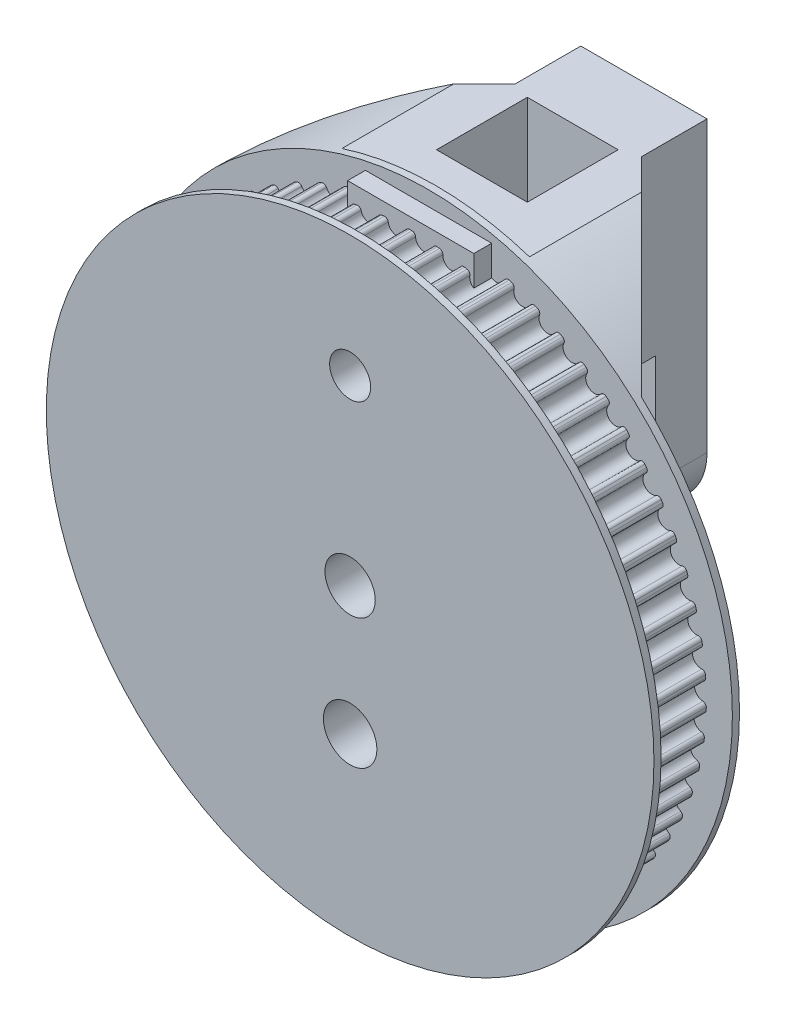
SolidWorks part; units mm, degrees
other "Markup1"
sketch "Sketch12" plane through (-30, -58, 49.7) normal (-0.8709, -0.4905, 0.0319) x (-0.1533, 0.2093, -0.9658)
other "Markup2"
sketch "Sketch14" plane through (30, -60, 49.7) normal (0.6168, -0.7172, 0.3243) x (-0.4689, -0.0038, 0.8832)
material "PETG"
ref_plane "Front Plane" through (0, 0, 0) normal (0, 0, 1) x (1, 0, 0)
ref_plane "Top Plane" through (0, 0, 0) normal (0, 1, 0) x (1, 0, 0)
ref_plane "Right Plane" through (0, 0, 0) normal (1, 0, 0) x (0, 0, -1)
sketch "Sketch1" plane through (0, 0, 0) normal (0, 1, 0) x (1, 0, 0)
  line L1 (-12.7375, -12.7375) -> (12.7375, -12.7375)
  line L2 (-12.7375, -12.7375) -> (-12.7375, 12.7375)
  line L3 (-12.7375, 12.7375) -> (12.7375, 12.7375)
  line L4 (12.7375, -12.7375) -> (12.7375, 12.7375)
  line L5 (-17.7, -17.7) -> (17.7, -17.7)
  line L6 (-17.7, -17.7) -> (-17.7, 17.7)
  line L7 (-17.7, 17.7) -> (17.7, 17.7)
  line L8 (17.7, -17.7) -> (17.7, 17.7)
  point P8 (0, -17.7)
  point P9 (0, -12.7375)
  point P12 (-17.7, 0)
  point P13 (-12.7375, 0)
  dimension "D1" = 25.475
  dimension "D2" = 35.4
extrude "Boss-Extrude1" add sketch "Sketch1" along normal blind 47.0375
extrude "Boss-Extrude2" add sketch "Sketch1<3>" against normal blind 14.9625 contours L1 L4 L3 L2 | L5 L8 L7 L6 L4 L1 L2 L3 region at (0, 0, 0) region at (-17.1994, 0, 0)
sketch "Sketch1<3>" plane through (0, 0, 0) normal (0, 1, 0) x (1, 0, 0) same geometry as "Sketch1"
sketch "Sketch3" plane through (0, 0, 0) normal (0, -1, 0) x (-1, 0, 0)
  circle A0 centre (0, 0) radius 3.15
  dimension "D1" = 6.3
extrude "Cut-Extrude1" cut sketch "Sketch3" along normal through all
sketch "Sketch13" plane through (0, -14.9625, 0) normal (0, -1, 0) x (1, 0, 0)
  circle A0 centre (0, 0) radius 5.5
  dimension "D1" = 11
extrude "Cut-Extrude4" cut sketch "Sketch13" against normal offset from surface (6.9625 mm away) 8 up to face at (0, 0, -3.15)
sketch "Sketch4" plane through (0, 0, 17.7) normal (0, 0, 1) x (1, 0, 0)
  line L0 (17.7, 47.0375) -> (17.7, -14.9625) construction
  line L1 (-17.7, 47.0375) -> (-17.7, -14.9625) construction
  line L2 (17.7, -34.0125) -> (17.7, -14.9625)
  line L3 (-17.7, -34.0125) -> (-17.7, -14.9625)
  line L5 (17.7, 47.0375) -> (-17.7, 47.0375)
  line L6 (17.7, 47.0375) -> (17.7, -14.9625)
  line L8 (-17.7, 47.0375) -> (-17.7, -14.9625)
  line L9 (-17.7, -14.9625) -> (17.7, -14.9625) construction
  line L10 (-17.7, 47.0375) -> (17.7, 47.0375) construction
  arc A0 (-17.7, -34.0125) -> (17.7, -34.0125) centre (0, -34.0125) ccw
  circle A1 centre (0, -34.0125) radius 7.05
  dimension "D2" = 14.1
  dimension "D1" = 19.05
extrude "Boss-Extrude3" add sketch "Sketch4" along normal blind 15
sketch "Sketch6" plane through (0, 0, 17.7) normal (0, 0, -1) x (-1, 0, 0)
  line L0 (17.7, -34.0125) -> (17.7, -14.9625)
  line L1 (17.7, -14.9625) -> (-17.7, -14.9625)
  line L2 (-17.7, -14.9625) -> (-17.7, -34.0125)
  arc A0 (-17.7, -34.0125) -> (17.7, -34.0125) centre (0, -34.0125) ccw
  arc A4 (-17.7, -34.0125) -> (17.7, -34.0125) centre (0, -34.0125) ccw construction
extrude "Cut-Extrude2" cut sketch "Sketch6" against normal blind 0.5375
sketch "Sketch7" plane through (0, 0, 18.2375) normal (0, 0, -1) x (-1, 0, 0)
  circle A0 centre (0, -34.0125) radius 11.0375
  arc A1 (-17.7, -34.0125) -> (17.7, -34.0125) centre (0, -34.0125) ccw construction
  dimension "D1" = 22.075
extrude "Cut-Extrude3" cut sketch "Sketch7" against normal blind 7
mirror "Mirror1" about plane through (0, 0, 0) normal (0, 0, 1) of "Boss-Extrude3", "Cut-Extrude2", "Cut-Extrude1", "Cut-Extrude3"
sketch "Sketch18" plane through (0, 0, 0) normal (0, 0, 1) x (1, 0, 0)
  line L0 (0, -13.5166) -> (-17.7, -3.2975)
  line L1 (-17.7, -3.2975) -> (-35.45, -34.0414) construction
  line L2 (-35.45, -34.0414) -> (-8.875, -49.3845) construction
  line L3 (-17.7, 47.0375) -> (-17.7, -34.0125) construction
  line L4 (0, -35.0322) -> (0, -50035.0322) construction
  line L5 (-17.7, -3.2975) -> (-17.7, -14.9625)
  line L6 (17.7, -34.0125) -> (17.7, 47.0375) construction
  line L7 (17.7, -3.2975) -> (0, -13.5166)
  line L10 (17.7, -14.9625) -> (17.7, -3.2975)
  line L11 (-17.7, -14.9625) -> (17.7, -14.9625)
  line L12 (-5.5, -14.9625) -> (5.5, -14.9625) construction
  circle A0 centre (0, -34.0125) radius 17.75 construction
  arc A2 (-17.7, -34.0125) -> (17.7, -34.0125) centre (0, -34.0125) ccw construction
  dimension "D2" = 120
  dimension "D1" = 35.5
extrude "Cut-Extrude10" cut sketch "Sketch18" along normal up to surface and the other way up to surface up to face at (-11.0375, -34.0125, 18.2375) other way up to face at (-11.0375, -34.0125, -18.2375)
ref_plane "Plane1" through (0, 0, 27.7) normal (0, 0, 1) x (1, 0, 0)
sketch "Sketch9" plane through (0, 0, 27.7) normal (0, 0, 1) x (1, 0, 0)
  circle A0 centre (0, -34.0125) radius 85.2141
  circle A1 centre (0, -34.0125) radius 7.05 construction
  circle A2 centre (0, -34.0125) radius 7.05
  dimension "D1" = 170.4282
extrude "Boss-Extrude4" add sketch "Sketch9" against normal blind 2 contours A0 region at (-82.8039, -34.0125, 27.7)
sketch "Sketch10" plane through (0, 0, 27.7) normal (0, 0, -1) x (-1, 0, 0)
  line L0 (0, -41.0625) -> (0, -50041.0625) construction
  line L1 (0, -34.0125) -> (-3.9983, -114.1269) construction
  line L2 (0, -34.0125) -> (3.9983, -114.1269) construction
  circle A0 centre (0, -34.0125) radius 80.2141 construction
  circle A1 centre (0, -34.0125) radius 7.05
  circle A2 centre (0, -34.0125) radius 85.2141 construction
  circle A3 centre (0, -34.0125) radius 7.05 construction
  arc A4 (2.4815, -110.9206) -> (-2.4815, -110.9206) centre (0, -111.1266) ccw
  arc A5 (-3.5233, -111.8369) -> (-2.4815, -110.9206) centre (-3.478, -110.8379) ccw
  circle A6 centre (0, -34.0125) radius 77.9041 construction
  arc A7 (2.4815, -110.9206) -> (3.5233, -111.8369) centre (3.478, -110.8379) ccw
  arc A8 (3.5233, -111.8369) -> (3.8832, -111.8198) centre (0, -34.0125) ccw
  arc A9 (-3.8832, -111.8198) -> (-3.5233, -111.8369) centre (0, -34.0125) ccw
  arc A10 (-11.611, -111.0465) -> (-11.2546, -111.0993) centre (0, -34.0125) ccw
  arc A11 (-11.2546, -111.0993) -> (-10.1267, -110.2914) centre (-11.1101, -110.1098) ccw
  arc A12 (-5.1884, -110.7855) -> (-10.1267, -110.2914) centre (-7.6781, -110.7434) ccw
  arc A13 (-5.1884, -110.7855) -> (-4.243, -111.801) centre (-4.1886, -110.8024) ccw
  arc A14 (-4.243, -111.801) -> (-3.8832, -111.8198) centre (0, -34.0125) ccw
  arc A15 (-19.2234, -109.5076) -> (-18.874, -109.5957) centre (0, -34.0125) ccw
  arc A16 (-18.874, -109.5957) -> (-17.6713, -108.904) centre (-18.6317, -108.6255) ccw
  arc A17 (-12.8068, -109.8874) -> (-17.6713, -108.904) centre (-15.2799, -109.5976) ccw
  arc A18 (-12.8068, -109.8874) -> (-11.9672, -110.9919) centre (-11.8136, -110.0038) ccw
  arc A19 (-11.9672, -110.9919) -> (-11.611, -111.0465) centre (0, -34.0125) ccw
  arc A20 (-26.6448, -107.2184) -> (-26.3059, -107.3409) centre (0, -34.0125) ccw
  arc A21 (-26.3059, -107.3409) -> (-25.0403, -106.7724) centre (-25.9682, -106.3996) ccw
  arc A22 (-20.2978, -108.2352) -> (-25.0403, -106.7724) centre (-22.7298, -107.7006) ccw
  arc A23 (-20.2978, -108.2352) -> (-19.5724, -109.4179) centre (-19.3212, -108.4499) ccw
  arc A24 (-19.5724, -109.4179) -> (-19.2234, -109.5076) centre (0, -34.0125) ccw
  arc A25 (-33.8013, -104.2017) -> (-33.4763, -104.3573) centre (0, -34.0125) ccw
  arc A26 (-33.4763, -104.3573) -> (-32.1604, -103.9176) centre (-33.0466, -103.4543) ccw
  arc A27 (-27.5872, -105.8454) -> (-32.1604, -103.9176) centre (-29.9538, -105.0713) ccw
  arc A28 (-27.5872, -105.8454) -> (-26.9831, -107.0944) centre (-26.6367, -106.1563) ccw
  arc A29 (-26.9831, -107.0944) -> (-26.6448, -107.2184) centre (0, -34.0125) ccw
  arc A30 (-40.6219, -100.4874) -> (-40.314, -100.6745) centre (0, -34.0125) ccw
  arc A31 (-40.314, -100.6745) -> (-38.9609, -100.3681) centre (-39.7965, -99.8188) ccw
  arc A32 (-34.6023, -102.7416) -> (-38.9609, -100.3681) centre (-36.8801, -101.7358) ccw
  arc A33 (-34.6023, -102.7416) -> (-34.1256, -104.0446) centre (-33.6876, -103.1456) ccw
  arc A34 (-34.1256, -104.0446) -> (-33.8013, -104.2017) centre (0, -34.0125) ccw
  arc A35 (-47.0388, -96.1124) -> (-46.7511, -96.3293) centre (0, -34.0125) ccw
  arc A36 (-46.7511, -96.3293) -> (-45.3742, -96.1591) centre (-46.151, -95.5294) ccw
  arc A37 (-41.2736, -98.9548) -> (-45.3742, -96.1591) centre (-43.4399, -97.7272) ccw
  arc A38 (-41.2736, -98.9548) -> (-40.929, -100.2987) centre (-40.4036, -99.4479) ccw
  arc A39 (-40.929, -100.2987) -> (-40.6219, -100.4874) centre (0, -34.0125) ccw
  arc A40 (-52.9882, -91.1202) -> (-52.7235, -91.3647) centre (0, -34.0125) ccw
  arc A41 (-52.7235, -91.3647) -> (-51.3365, -91.3325) centre (-52.0467, -90.6285) ccw
  arc A42 (-47.5347, -94.5226) -> (-51.3365, -91.3325) centre (-49.568, -93.0853) ccw
  arc A43 (-47.5347, -94.5226) -> (-47.3256, -95.8941) centre (-46.7181, -95.0998) ccw
  arc A44 (-47.3256, -95.8941) -> (-47.0388, -96.1124) centre (0, -34.0125) ccw
  arc A45 (-58.411, -85.5605) -> (-58.172, -85.8302) centre (0, -34.0125) ccw
  arc A46 (-58.172, -85.8302) -> (-56.7886, -85.9362) centre (-57.4253, -85.165) ccw
  arc A47 (-53.3233, -89.489) -> (-56.7886, -85.9362) centre (-55.2034, -87.8564) ccw
  arc A48 (-53.3233, -89.489) -> (-53.2518, -90.8745) centre (-52.5683, -90.1446) ccw
  arc A49 (-53.2518, -90.8745) -> (-52.9882, -91.1202) centre (0, -34.0125) ccw
  arc A50 (-63.2533, -79.4885) -> (-63.0423, -79.7806) centre (0, -34.0125) ccw
  arc A51 (-63.0423, -79.7806) -> (-61.6764, -80.0238) centre (-62.233, -79.1931) ccw
  arc A52 (-58.582, -83.904) -> (-61.6764, -80.0238) centre (-60.2902, -82.0923) ccw
  arc A53 (-58.582, -83.904) -> (-58.6488, -85.2898) centre (-57.896, -84.6316) ccw
  arc A54 (-58.6488, -85.2898) -> (-58.411, -85.5605) centre (0, -34.0125) ccw
  arc A55 (-67.4669, -72.9645) -> (-67.286, -73.2762) centre (0, -34.0125) ccw
  arc A56 (-67.286, -73.2762) -> (-65.9511, -73.6542) centre (-66.4223, -72.7722) ccw
  arc A57 (-63.2585, -77.8232) -> (-65.9511, -73.6542) centre (-64.7778, -75.8505) ccw
  arc A58 (-63.2585, -77.8232) -> (-63.463, -79.1955) centre (-62.6483, -78.6155) ccw
  arc A59 (-63.463, -79.1955) -> (-63.2533, -79.4885) centre (0, -34.0125) ccw
  arc A60 (-71.01, -66.0534) -> (-70.8611, -66.3816) centre (0, -34.0125) ccw
  arc A61 (-70.8611, -66.3816) -> (-69.5704, -66.8906) centre (-69.9515, -65.9661) ccw
  arc A62 (-67.3063, -71.307) -> (-69.5704, -66.8906) centre (-68.6217, -69.1928) ccw
  arc A63 (-67.3063, -71.307) -> (-67.6464, -72.6521) centre (-66.778, -72.1561) ccw
  arc A64 (-67.6464, -72.6521) -> (-67.4669, -72.9645) centre (0, -34.0125) ccw
  arc A65 (-73.8474, -58.8239) -> (-73.7319, -59.1652) centre (0, -34.0125) ccw
  arc A66 (-73.7319, -59.1652) -> (-72.4983, -59.8003) centre (-72.7854, -58.8424) ccw
  arc A67 (-70.6852, -64.4201) -> (-72.4983, -59.8003) centre (-71.7835, -62.1854) ccw
  arc A68 (-70.6852, -64.4201) -> (-71.1575, -65.7247) centre (-70.2441, -65.3176) ccw
  arc A69 (-71.1575, -65.7247) -> (-71.01, -66.0534) centre (0, -34.0125) ccw
  arc A70 (-75.9509, -51.3478) -> (-75.8699, -51.6989) centre (0, -34.0125) ccw
  arc A71 (-75.8699, -51.6989) -> (-74.7057, -52.4536) centre (-74.896, -51.4719) ccw
  arc A72 (-73.3615, -57.2311) -> (-74.7057, -52.4536) centre (-74.2319, -54.8981) ccw
  arc A73 (-73.3615, -57.2311) -> (-73.9614, -58.4821) centre (-73.012, -58.168) ccw
  arc A74 (-73.9614, -58.4821) -> (-73.8474, -58.8239) centre (0, -34.0125) ccw
  arc A75 (-77.2995, -43.6994) -> (-77.2539, -44.0568) centre (0, -34.0125) ccw
  arc A76 (-77.2539, -44.0568) -> (-76.1706, -44.9237) centre (-76.2622, -43.9279) ccw
  arc A77 (-75.3088, -49.8112) -> (-76.1706, -44.9237) centre (-75.9426, -47.4032) ccw
  arc A78 (-75.3088, -49.8112) -> (-76.0302, -50.9963) centre (-75.0543, -50.7783) ccw
  arc A79 (-76.0302, -50.9963) -> (-75.9509, -51.3478) centre (0, -34.0125) ccw
  arc A80 (-77.8799, -35.9547) -> (-77.8701, -36.3149) centre (0, -34.0125) ccw
  arc A81 (-77.8701, -36.3149) -> (-76.8785, -37.2853) centre (-76.8705, -36.2854) ccw
  arc A82 (-76.5076, -42.2344) -> (-76.8785, -37.2853) centre (-76.8985, -39.7752) ccw
  arc A83 (-76.5076, -42.2344) -> (-77.3435, -43.3417) centre (-76.3507, -43.222) ccw
  arc A84 (-77.3435, -43.3417) -> (-77.2995, -43.6994) centre (0, -34.0125) ccw
  arc A85 (-77.6863, -28.1907) -> (-77.7124, -28.5501) centre (0, -34.0125) ccw
  arc A86 (-77.7124, -28.5501) -> (-76.8224, -29.6144) centre (-76.7148, -28.6202) ccw
  arc A87 (-76.9461, -34.5758) -> (-76.8224, -29.6144) centre (-77.0901, -32.09) ccw
  arc A88 (-76.9461, -34.5758) -> (-77.888, -35.5945) centre (-76.8882, -35.5741) ccw
  arc A89 (-77.888, -35.5945) -> (-77.8799, -35.9547) centre (0, -34.0125) ccw
  arc A90 (-76.7206, -20.4846) -> (-76.7823, -20.8396) centre (0, -34.0125) ccw
  arc A91 (-76.7823, -20.8396) -> (-76.0027, -21.9873) centre (-75.7967, -21.0087) ccw
  arc A92 (-76.6198, -26.9117) -> (-76.0027, -21.9873) centre (-76.5156, -24.4238) ccw
  arc A93 (-76.6198, -26.9117) -> (-77.6585, -27.8315) centre (-76.6616, -27.9108) ccw
  arc A94 (-77.6585, -27.8315) -> (-77.6863, -28.1907) centre (0, -34.0125) ccw
  arc A95 (-74.9924, -12.9129) -> (-75.0892, -13.26) centre (0, -34.0125) ccw
  arc A96 (-75.0892, -13.26) -> (-74.4277, -14.4796) centre (-74.1253, -13.5264) ccw
  arc A97 (-75.5321, -19.3181) -> (-74.4277, -14.4796) centre (-75.1807, -16.853) ccw
  arc A98 (-75.5321, -19.3181) -> (-76.6572, -20.1299) centre (-75.6732, -20.3081) ccw
  arc A99 (-76.6572, -20.1299) -> (-76.7206, -20.4846) centre (0, -34.0125) ccw
  arc A100 (-72.5189, -5.5509) -> (-72.6497, -5.8867) centre (0, -34.0125) ccw
  arc A101 (-72.6497, -5.8867) -> (-72.113, -7.166) centre (-71.7172, -6.2477) ccw
  arc A102 (-73.6936, -11.8705) -> (-72.113, -7.166) centre (-73.0986, -9.4527) ccw
  arc A103 (-73.6936, -11.8705) -> (-74.894, -12.5663) centre (-73.9326, -12.8416) ccw
  arc A104 (-74.894, -12.5663) -> (-74.9924, -12.9129) centre (0, -34.0125) ccw
  arc A105 (-69.3247, 1.5282) -> (-69.4883, 1.2071) centre (0, -34.0125) ccw
  arc A106 (-69.4883, 1.2071) -> (-69.0816, -0.1193) centre (-68.5963, 0.7551) ccw
  arc A107 (-71.1228, -4.6431) -> (-69.0816, -0.1193) centre (-70.2899, -2.2965) ccw
  arc A108 (-71.1228, -4.6431) -> (-72.3865, -5.2158) centre (-71.4573, -5.5855) ccw
  arc A109 (-72.3865, -5.2158) -> (-72.5189, -5.5509) centre (0, -34.0125) ccw
  arc A110 (-65.4415, 8.2541) -> (-65.6363, 7.9509) centre (0, -34.0125) ccw
  arc A111 (-65.6363, 7.9509) -> (-65.3637, 6.5906) centre (-64.7937, 7.4123) ccw
  arc A112 (-67.8451, 2.2925) -> (-65.3637, 6.5906) centre (-66.7828, 4.5445) ccw
  arc A113 (-67.8451, 2.2925) -> (-69.1595, 1.8485) centre (-68.2718, 1.3881) ccw
  arc A114 (-69.1595, 1.8485) -> (-69.3247, 1.5282) centre (0, -34.0125) ccw
  arc A115 (-60.9079, 14.5599) -> (-61.1319, 14.2777) centre (0, -34.0125) ccw
  arc A116 (-61.1319, 14.2777) -> (-60.9961, 12.8969) centre (-60.3472, 13.6578) ccw
  arc A117 (-63.8932, 8.8673) -> (-60.9961, 12.8969) centre (-62.6119, 11.0024) ccw
  arc A118 (-63.8932, 8.8673) -> (-65.2453, 8.5563) centre (-64.4077, 8.0099) ccw
  arc A119 (-65.2453, 8.5563) -> (-65.4415, 8.2541) centre (0, -34.0125) ccw
  arc A120 (-55.769, 20.383) -> (-56.02, 20.1245) centre (0, -34.0125) ccw
  arc A121 (-56.02, 20.1245) -> (-56.0223, 18.7371) centre (-55.3009, 19.4295) ccw
  arc A122 (-59.3062, 15.016) -> (-56.0223, 18.7371) centre (-57.8187, 17.0128) ccw
  arc A123 (-59.3062, 15.016) -> (-60.6826, 14.8411) centre (-59.9036, 14.214) ccw
  arc A124 (-60.6826, 14.8411) -> (-60.9079, 14.5599) centre (0, -34.0125) ccw
  arc A125 (-50.0758, 25.6655) -> (-50.3513, 25.4332) centre (0, -34.0125) ccw
  arc A126 (-50.3513, 25.4332) -> (-50.4918, 24.053) centre (-49.705, 24.6702) ccw
  arc A127 (-54.1299, 20.6773) -> (-50.4918, 24.053) centre (-52.4509, 22.5161) ccw
  arc A128 (-54.1299, 20.6773) -> (-55.5168, 20.6404) centre (-54.8041, 19.9388) ccw
  arc A129 (-55.5168, 20.6404) -> (-55.769, 20.383) centre (0, -34.0125) ccw
  arc A130 (-43.8849, 30.3549) -> (-44.1822, 30.1512) centre (0, -34.0125) ccw
  arc A131 (-44.1822, 30.1512) -> (-44.4594, 28.7918) centre (-43.6151, 29.3276) ccw
  arc A132 (-48.4155, 25.7951) -> (-44.4594, 28.7918) centre (-46.5618, 27.4576) ccw
  arc A133 (-48.4155, 25.7951) -> (-49.7992, 25.8965) centre (-49.16, 25.1275) ccw
  arc A134 (-49.7992, 25.8965) -> (-50.0758, 25.6655) centre (0, -34.0125) ccw
  arc A135 (-37.2579, 34.4046) -> (-37.574, 34.2315) centre (0, -34.0125) ccw
  arc A136 (-37.574, 34.2315) -> (-37.9852, 32.9064) centre (-37.0917, 33.3555) ccw
  arc A137 (-42.22, 30.3186) -> (-37.9852, 32.9064) centre (-40.21, 31.7883) ccw
  arc A138 (-42.22, 30.3186) -> (-43.5867, 30.5572) centre (-43.0272, 29.7283) ccw
  arc A139 (-43.5867, 30.5572) -> (-43.8849, 30.3549) centre (0, -34.0125) ccw
  arc A140 (-30.2607, 37.7743) -> (-30.5924, 37.6335) centre (0, -34.0125) ccw
  arc A141 (-30.5924, 37.6335) -> (-31.1335, 36.356) centre (-30.1997, 36.7139) ccw
  arc A142 (-35.6049, 34.2027) -> (-31.1335, 36.356) centre (-33.4586, 35.4649) ccw
  arc A143 (-35.6049, 34.2027) -> (-36.9411, 34.5762) centre (-36.4669, 33.6957) ccw
  arc A144 (-36.9411, 34.5762) -> (-37.2579, 34.4046) centre (0, -34.0125) ccw
  arc A145 (-22.9626, 40.4305) -> (-23.3067, 40.3235) centre (0, -34.0125) ccw
  arc A146 (-23.3067, 40.3235) -> (-23.9723, 39.1062) centre (-23.0075, 39.3693) ccw
  arc A147 (-28.6359, 37.4088) -> (-23.9723, 39.1062) centre (-26.3746, 38.451) ccw
  arc A148 (-28.6359, 37.4088) -> (-29.9283, 37.9135) centre (-29.5441, 36.9902) ccw
  arc A149 (-29.9283, 37.9135) -> (-30.2607, 37.7743) centre (0, -34.0125) ccw
  arc A150 (-15.4364, 42.3469) -> (-15.7894, 42.2747) centre (0, -34.0125) ccw
  arc A151 (-15.7894, 42.2747) -> (-16.5729, 41.1297) centre (-15.5867, 41.2955) ccw
  arc A152 (-21.3824, 39.9051) -> (-16.5729, 41.1297) centre (-19.0285, 40.717) ccw
  arc A153 (-21.3824, 39.9051) -> (-22.6181, 40.5359) centre (-22.3277, 39.579) ccw
  arc A154 (-22.6181, 40.5359) -> (-22.9626, 40.4305) centre (0, -34.0125) ccw
  arc A155 (-7.7567, 43.5045) -> (-8.1152, 43.4678) centre (0, -34.0125) ccw
  arc A156 (-8.1152, 43.4678) -> (-9.0088, 42.4065) centre (-8.011, 42.4732) ccw
  arc A157 (-13.9163, 41.6668) -> (-9.0088, 42.4065) centre (-11.4933, 42.2403) ccw
  arc A158 (-13.9163, 41.6668) -> (-15.083, 42.4175) centre (-14.8894, 41.4365) ccw
  arc A159 (-15.083, 42.4175) -> (-15.4364, 42.3469) centre (0, -34.0125) ccw
  arc A160 (0, 43.8916) -> (-0.3603, 43.8908) centre (0, -34.0125) ccw
  arc A161 (-0.3603, 43.8908) -> (-1.3552, 42.9237) centre (-0.3557, 42.8908) ccw
  arc A162 (-6.3119, 42.6763) -> (-1.3552, 42.9237) centre (-3.8438, 43.0057) ccw
  arc A163 (-6.3119, 42.6763) -> (-7.3981, 43.5395) centre (-7.3031, 42.544) ccw
  arc A164 (-7.3981, 43.5395) -> (-7.7567, 43.5045) centre (0, -34.0125) ccw
  arc A165 (7.7567, 43.5045) -> (7.3981, 43.5395) centre (0, -34.0125) ccw
  arc A166 (7.3981, 43.5395) -> (6.3119, 42.6763) centre (7.3031, 42.544) ccw
  arc A167 (1.3552, 42.9237) -> (6.3119, 42.6763) centre (3.8438, 43.0057) ccw
  arc A168 (1.3552, 42.9237) -> (0.3603, 43.8908) centre (0.3557, 42.8908) ccw
  arc A169 (0.3603, 43.8908) -> (0, 43.8916) centre (0, -34.0125) ccw
  arc A170 (15.4364, 42.3469) -> (15.083, 42.4175) centre (0, -34.0125) ccw
  arc A171 (15.083, 42.4175) -> (13.9163, 41.6668) centre (14.8894, 41.4365) ccw
  arc A172 (9.0088, 42.4065) -> (13.9163, 41.6668) centre (11.4933, 42.2403) ccw
  arc A173 (9.0088, 42.4065) -> (8.1152, 43.4678) centre (8.011, 42.4732) ccw
  arc A174 (8.1152, 43.4678) -> (7.7567, 43.5045) centre (0, -34.0125) ccw
  arc A175 (22.9626, 40.4305) -> (22.6181, 40.5359) centre (0, -34.0125) ccw
  arc A176 (22.6181, 40.5359) -> (21.3824, 39.9051) centre (22.3277, 39.579) ccw
  arc A177 (16.5729, 41.1297) -> (21.3824, 39.9051) centre (19.0285, 40.717) ccw
  arc A178 (16.5729, 41.1297) -> (15.7894, 42.2747) centre (15.5867, 41.2955) ccw
  arc A179 (15.7894, 42.2747) -> (15.4364, 42.3469) centre (0, -34.0125) ccw
  arc A180 (30.2607, 37.7743) -> (29.9283, 37.9135) centre (0, -34.0125) ccw
  arc A181 (29.9283, 37.9135) -> (28.6359, 37.4088) centre (29.5441, 36.9902) ccw
  arc A182 (23.9723, 39.1062) -> (28.6359, 37.4088) centre (26.3746, 38.451) ccw
  arc A183 (23.9723, 39.1062) -> (23.3067, 40.3235) centre (23.0075, 39.3693) ccw
  arc A184 (23.3067, 40.3235) -> (22.9626, 40.4305) centre (0, -34.0125) ccw
  arc A185 (37.2579, 34.4046) -> (36.9411, 34.5762) centre (0, -34.0125) ccw
  arc A186 (36.9411, 34.5762) -> (35.6049, 34.2027) centre (36.4669, 33.6957) ccw
  arc A187 (31.1335, 36.356) -> (35.6049, 34.2027) centre (33.4586, 35.4649) ccw
  arc A188 (31.1335, 36.356) -> (30.5924, 37.6335) centre (30.1997, 36.7139) ccw
  arc A189 (30.5924, 37.6335) -> (30.2607, 37.7743) centre (0, -34.0125) ccw
  arc A190 (43.8849, 30.3549) -> (43.5867, 30.5572) centre (0, -34.0125) ccw
  arc A191 (43.5867, 30.5572) -> (42.22, 30.3186) centre (43.0272, 29.7283) ccw
  arc A192 (37.9852, 32.9064) -> (42.22, 30.3186) centre (40.21, 31.7883) ccw
  arc A193 (37.9852, 32.9064) -> (37.574, 34.2315) centre (37.0917, 33.3555) ccw
  arc A194 (37.574, 34.2315) -> (37.2579, 34.4046) centre (0, -34.0125) ccw
  arc A195 (50.0758, 25.6655) -> (49.7992, 25.8965) centre (0, -34.0125) ccw
  arc A196 (49.7992, 25.8965) -> (48.4155, 25.7951) centre (49.16, 25.1275) ccw
  arc A197 (44.4594, 28.7918) -> (48.4155, 25.7951) centre (46.5618, 27.4576) ccw
  arc A198 (44.4594, 28.7918) -> (44.1822, 30.1512) centre (43.6151, 29.3276) ccw
  arc A199 (44.1822, 30.1512) -> (43.8849, 30.3549) centre (0, -34.0125) ccw
  arc A200 (55.769, 20.383) -> (55.5168, 20.6404) centre (0, -34.0125) ccw
  arc A201 (55.5168, 20.6404) -> (54.1299, 20.6773) centre (54.8041, 19.9388) ccw
  arc A202 (50.4918, 24.053) -> (54.1299, 20.6773) centre (52.4509, 22.5161) ccw
  arc A203 (50.4918, 24.053) -> (50.3513, 25.4332) centre (49.705, 24.6702) ccw
  arc A204 (50.3513, 25.4332) -> (50.0758, 25.6655) centre (0, -34.0125) ccw
  arc A205 (60.9079, 14.5599) -> (60.6826, 14.8411) centre (0, -34.0125) ccw
  arc A206 (60.6826, 14.8411) -> (59.3062, 15.016) centre (59.9036, 14.214) ccw
  arc A207 (56.0223, 18.7371) -> (59.3062, 15.016) centre (57.8187, 17.0128) ccw
  arc A208 (56.0223, 18.7371) -> (56.02, 20.1245) centre (55.3009, 19.4295) ccw
  arc A209 (56.02, 20.1245) -> (55.769, 20.383) centre (0, -34.0125) ccw
  arc A210 (65.4415, 8.2541) -> (65.2453, 8.5563) centre (0, -34.0125) ccw
  arc A211 (65.2453, 8.5563) -> (63.8932, 8.8673) centre (64.4077, 8.0099) ccw
  arc A212 (60.9961, 12.8969) -> (63.8932, 8.8673) centre (62.6119, 11.0024) ccw
  arc A213 (60.9961, 12.8969) -> (61.1319, 14.2777) centre (60.3472, 13.6578) ccw
  arc A214 (61.1319, 14.2777) -> (60.9079, 14.5599) centre (0, -34.0125) ccw
  arc A215 (69.3247, 1.5282) -> (69.1595, 1.8485) centre (0, -34.0125) ccw
  arc A216 (69.1595, 1.8485) -> (67.8451, 2.2925) centre (68.2718, 1.3881) ccw
  arc A217 (65.3637, 6.5906) -> (67.8451, 2.2925) centre (66.7828, 4.5445) ccw
  arc A218 (65.3637, 6.5906) -> (65.6363, 7.9509) centre (64.7937, 7.4123) ccw
  arc A219 (65.6363, 7.9509) -> (65.4415, 8.2541) centre (0, -34.0125) ccw
  arc A220 (72.5189, -5.5509) -> (72.3865, -5.2158) centre (0, -34.0125) ccw
  arc A221 (72.3865, -5.2158) -> (71.1228, -4.6431) centre (71.4573, -5.5855) ccw
  arc A222 (69.0816, -0.1193) -> (71.1228, -4.6431) centre (70.2899, -2.2965) ccw
  arc A223 (69.0816, -0.1193) -> (69.4883, 1.2071) centre (68.5963, 0.7551) ccw
  arc A224 (69.4883, 1.2071) -> (69.3247, 1.5282) centre (0, -34.0125) ccw
  arc A225 (74.9924, -12.9129) -> (74.894, -12.5663) centre (0, -34.0125) ccw
  arc A226 (74.894, -12.5663) -> (73.6936, -11.8705) centre (73.9326, -12.8416) ccw
  arc A227 (72.113, -7.166) -> (73.6936, -11.8705) centre (73.0986, -9.4527) ccw
  arc A228 (72.113, -7.166) -> (72.6497, -5.8867) centre (71.7172, -6.2477) ccw
  arc A229 (72.6497, -5.8867) -> (72.5189, -5.5509) centre (0, -34.0125) ccw
  arc A230 (76.7206, -20.4846) -> (76.6572, -20.1299) centre (0, -34.0125) ccw
  arc A231 (76.6572, -20.1299) -> (75.5321, -19.3181) centre (75.6732, -20.3081) ccw
  arc A232 (74.4277, -14.4796) -> (75.5321, -19.3181) centre (75.1807, -16.853) ccw
  arc A233 (74.4277, -14.4796) -> (75.0892, -13.26) centre (74.1253, -13.5264) ccw
  arc A234 (75.0892, -13.26) -> (74.9924, -12.9129) centre (0, -34.0125) ccw
  arc A235 (77.6863, -28.1907) -> (77.6585, -27.8315) centre (0, -34.0125) ccw
  arc A236 (77.6585, -27.8315) -> (76.6198, -26.9117) centre (76.6616, -27.9108) ccw
  arc A237 (76.0027, -21.9873) -> (76.6198, -26.9117) centre (76.5156, -24.4238) ccw
  arc A238 (76.0027, -21.9873) -> (76.7823, -20.8396) centre (75.7967, -21.0087) ccw
  arc A239 (76.7823, -20.8396) -> (76.7206, -20.4846) centre (0, -34.0125) ccw
  arc A240 (77.8799, -35.9547) -> (77.888, -35.5945) centre (0, -34.0125) ccw
  arc A241 (77.888, -35.5945) -> (76.9461, -34.5758) centre (76.8882, -35.5741) ccw
  arc A242 (76.8224, -29.6144) -> (76.9461, -34.5758) centre (77.0901, -32.09) ccw
  arc A243 (76.8224, -29.6144) -> (77.7124, -28.5501) centre (76.7148, -28.6202) ccw
  arc A244 (77.7124, -28.5501) -> (77.6863, -28.1907) centre (0, -34.0125) ccw
  arc A245 (77.2995, -43.6994) -> (77.3435, -43.3417) centre (0, -34.0125) ccw
  arc A246 (77.3435, -43.3417) -> (76.5076, -42.2344) centre (76.3507, -43.222) ccw
  arc A247 (76.8785, -37.2853) -> (76.5076, -42.2344) centre (76.8985, -39.7752) ccw
  arc A248 (76.8785, -37.2853) -> (77.8701, -36.3149) centre (76.8705, -36.2854) ccw
  arc A249 (77.8701, -36.3149) -> (77.8799, -35.9547) centre (0, -34.0125) ccw
  arc A250 (75.9509, -51.3478) -> (76.0302, -50.9963) centre (0, -34.0125) ccw
  arc A251 (76.0302, -50.9963) -> (75.3088, -49.8112) centre (75.0543, -50.7783) ccw
  arc A252 (76.1706, -44.9237) -> (75.3088, -49.8112) centre (75.9426, -47.4032) ccw
  arc A253 (76.1706, -44.9237) -> (77.2539, -44.0568) centre (76.2622, -43.9279) ccw
  arc A254 (77.2539, -44.0568) -> (77.2995, -43.6994) centre (0, -34.0125) ccw
  arc A255 (73.8474, -58.8239) -> (73.9614, -58.4821) centre (0, -34.0125) ccw
  arc A256 (73.9614, -58.4821) -> (73.3615, -57.2311) centre (73.012, -58.168) ccw
  arc A257 (74.7057, -52.4536) -> (73.3615, -57.2311) centre (74.2319, -54.8981) ccw
  arc A258 (74.7057, -52.4536) -> (75.8699, -51.6989) centre (74.896, -51.4719) ccw
  arc A259 (75.8699, -51.6989) -> (75.9509, -51.3478) centre (0, -34.0125) ccw
  arc A260 (71.01, -66.0534) -> (71.1575, -65.7247) centre (0, -34.0125) ccw
  arc A261 (71.1575, -65.7247) -> (70.6852, -64.4201) centre (70.2441, -65.3176) ccw
  arc A262 (72.4983, -59.8003) -> (70.6852, -64.4201) centre (71.7835, -62.1854) ccw
  arc A263 (72.4983, -59.8003) -> (73.7319, -59.1652) centre (72.7854, -58.8424) ccw
  arc A264 (73.7319, -59.1652) -> (73.8474, -58.8239) centre (0, -34.0125) ccw
  arc A265 (67.4669, -72.9645) -> (67.6464, -72.6521) centre (0, -34.0125) ccw
  arc A266 (67.6464, -72.6521) -> (67.3063, -71.307) centre (66.778, -72.1561) ccw
  arc A267 (69.5704, -66.8906) -> (67.3063, -71.307) centre (68.6217, -69.1928) ccw
  arc A268 (69.5704, -66.8906) -> (70.8611, -66.3816) centre (69.9515, -65.9661) ccw
  arc A269 (70.8611, -66.3816) -> (71.01, -66.0534) centre (0, -34.0125) ccw
  arc A270 (63.2533, -79.4885) -> (63.463, -79.1955) centre (0, -34.0125) ccw
  arc A271 (63.463, -79.1955) -> (63.2585, -77.8232) centre (62.6483, -78.6155) ccw
  arc A272 (65.9511, -73.6542) -> (63.2585, -77.8232) centre (64.7778, -75.8505) ccw
  arc A273 (65.9511, -73.6542) -> (67.286, -73.2762) centre (66.4223, -72.7722) ccw
  arc A274 (67.286, -73.2762) -> (67.4669, -72.9645) centre (0, -34.0125) ccw
  arc A275 (58.411, -85.5605) -> (58.6488, -85.2898) centre (0, -34.0125) ccw
  arc A276 (58.6488, -85.2898) -> (58.582, -83.904) centre (57.896, -84.6316) ccw
  arc A277 (61.6764, -80.0238) -> (58.582, -83.904) centre (60.2902, -82.0923) ccw
  arc A278 (61.6764, -80.0238) -> (63.0423, -79.7806) centre (62.233, -79.1931) ccw
  arc A279 (63.0423, -79.7806) -> (63.2533, -79.4885) centre (0, -34.0125) ccw
  arc A280 (52.9882, -91.1202) -> (53.2518, -90.8745) centre (0, -34.0125) ccw
  arc A281 (53.2518, -90.8745) -> (53.3233, -89.489) centre (52.5683, -90.1446) ccw
  arc A282 (56.7886, -85.9362) -> (53.3233, -89.489) centre (55.2034, -87.8564) ccw
  arc A283 (56.7886, -85.9362) -> (58.172, -85.8302) centre (57.4253, -85.165) ccw
  arc A284 (58.172, -85.8302) -> (58.411, -85.5605) centre (0, -34.0125) ccw
  arc A285 (47.0388, -96.1124) -> (47.3256, -95.8941) centre (0, -34.0125) ccw
  arc A286 (47.3256, -95.8941) -> (47.5347, -94.5226) centre (46.7181, -95.0998) ccw
  arc A287 (51.3365, -91.3325) -> (47.5347, -94.5226) centre (49.568, -93.0853) ccw
  arc A288 (51.3365, -91.3325) -> (52.7235, -91.3647) centre (52.0467, -90.6285) ccw
  arc A289 (52.7235, -91.3647) -> (52.9882, -91.1202) centre (0, -34.0125) ccw
  arc A290 (40.6219, -100.4874) -> (40.929, -100.2987) centre (0, -34.0125) ccw
  arc A291 (40.929, -100.2987) -> (41.2736, -98.9548) centre (40.4036, -99.4479) ccw
  arc A292 (45.3742, -96.1591) -> (41.2736, -98.9548) centre (43.4399, -97.7272) ccw
  arc A293 (45.3742, -96.1591) -> (46.7511, -96.3293) centre (46.151, -95.5294) ccw
  arc A294 (46.7511, -96.3293) -> (47.0388, -96.1124) centre (0, -34.0125) ccw
  arc A295 (33.8013, -104.2017) -> (34.1256, -104.0446) centre (0, -34.0125) ccw
  arc A296 (34.1256, -104.0446) -> (34.6023, -102.7416) centre (33.6876, -103.1456) ccw
  arc A297 (38.9609, -100.3681) -> (34.6023, -102.7416) centre (36.8801, -101.7358) ccw
  arc A298 (38.9609, -100.3681) -> (40.314, -100.6745) centre (39.7965, -99.8188) ccw
  arc A299 (40.314, -100.6745) -> (40.6219, -100.4874) centre (0, -34.0125) ccw
  arc A300 (26.6448, -107.2184) -> (26.9831, -107.0944) centre (0, -34.0125) ccw
  arc A301 (26.9831, -107.0944) -> (27.5872, -105.8454) centre (26.6367, -106.1563) ccw
  arc A302 (32.1604, -103.9176) -> (27.5872, -105.8454) centre (29.9538, -105.0713) ccw
  arc A303 (32.1604, -103.9176) -> (33.4763, -104.3573) centre (33.0466, -103.4543) ccw
  arc A304 (33.4763, -104.3573) -> (33.8013, -104.2017) centre (0, -34.0125) ccw
  arc A305 (19.2234, -109.5076) -> (19.5724, -109.4179) centre (0, -34.0125) ccw
  arc A306 (19.5724, -109.4179) -> (20.2978, -108.2352) centre (19.3212, -108.4499) ccw
  arc A307 (25.0403, -106.7724) -> (20.2978, -108.2352) centre (22.7298, -107.7006) ccw
  arc A308 (25.0403, -106.7724) -> (26.3059, -107.3409) centre (25.9682, -106.3996) ccw
  arc A309 (26.3059, -107.3409) -> (26.6448, -107.2184) centre (0, -34.0125) ccw
  arc A310 (11.611, -111.0465) -> (11.9672, -110.9919) centre (0, -34.0125) ccw
  arc A311 (11.9672, -110.9919) -> (12.8068, -109.8874) centre (11.8136, -110.0038) ccw
  arc A312 (17.6713, -108.904) -> (12.8068, -109.8874) centre (15.2799, -109.5976) ccw
  arc A313 (17.6713, -108.904) -> (18.874, -109.5957) centre (18.6317, -108.6255) ccw
  arc A314 (18.874, -109.5957) -> (19.2234, -109.5076) centre (0, -34.0125) ccw
  arc A315 (3.8832, -111.8198) -> (4.243, -111.801) centre (0, -34.0125) ccw
  arc A316 (4.243, -111.801) -> (5.1884, -110.7855) centre (4.1886, -110.8024) ccw
  arc A317 (10.1267, -110.2914) -> (5.1884, -110.7855) centre (7.6781, -110.7434) ccw
  arc A318 (10.1267, -110.2914) -> (11.2546, -111.0993) centre (11.1101, -110.1098) ccw
  arc A319 (11.2546, -111.0993) -> (11.611, -111.0465) centre (0, -34.0125) ccw
  point P10 (0, -108.6366)
  point P14 (0, -111.9166)
  point P27 (0, -114.2266)
  arc M13 (-17.7, -34.0125) -> (17.7, -34.0125) centre (0, -34.0125) ccw
  line M14 (17.7, -34.0125) -> (17.7, 47.0375)
  line M16 (-17.7, 47.0375) -> (-17.7, -34.0125)
  dimension "D1" = 160.4282
  dimension "D2" = 2.49
  dimension "D3" = 1
  dimension "D4" = 3.28
  dimension "D6" = 5.59
  dimension "D5" = 8
  dimension "D7" = 63
extrude "Boss-Extrude5" add sketch "Sketch10" against normal blind 20 contours A8 A7 A4 A5 A9 A14 A13 A12 A11 A10 A19 A18 A17 A16 A15 A24 A23 A22 A21 A20 A29 A28 A27 A26 A25 A34 A33 A32 A31 A30 A39 A38 A37 A36 A35 A44 A43 A42 A41 A40 A49 A48 A47 A46 A45 A54 | A179 A178 A177 A152 A151 A150 A159 A158 A157 A156 A155 A164 A163 A162 A161 A160 A169 A168 A167 A166 A165 A174 A173 A172 A171 A170 A1 M14 M13 M16 region at (0, -106.4572, 27.7) region at (0, -1.7178, 27.7)
sketch "Sketch11" plane through (0, 0, 47.7) normal (0, 0, 1) x (1, 0, 0)
  circle A0 centre (0, -34.0125) radius 85.2141
  circle A1 centre (0, -34.0125) radius 7.05
  circle A3 centre (0, -34.0125) radius 85.2141 construction
  circle A4 centre (0, -34.0125) radius 7.05 construction
extrude "Boss-Extrude6" add sketch "Sketch11" along normal blind 2 contours A0 region at (-82.8039, -34.0125, 47.7)
sketch "Sketch15" plane through (0, 0, -32.7) normal (0, 0, -1) x (-1, 0, 0)
  line L1 (0, 17.0375) -> (-17.7, 17.0375) construction
  line L2 (0, 17.0375) -> (17.7, 17.0375) construction
  line L3 (17.7, 47.0375) -> (17.7, -34.0125) construction
  line L4 (-17.7, -34.0125) -> (-17.7, 47.0375) construction
  line L5 (-17.7, 47.0375) -> (17.7, 47.0375) construction
  circle A0 centre (0, 17.0375) radius 3.25
  dimension "D1" = 6.5
  dimension "D2" = 30
extrude "Cut-Extrude5" cut sketch "Sketch15" against normal up to next
sketch "Sketch16" plane through (0, 0, -32.7) normal (0, 0, -1) x (-1, 0, 0)
  circle A0 centre (0, 17.0375) radius 5.75
  circle A1 centre (0, 17.0375) radius 3.25 construction
  dimension "D1" = 11.5
extrude "Cut-Extrude6" cut sketch "Sketch16" against normal blind 10 and the other way through all
mirror "Mirror2" about plane through (0, 0, 0) normal (0, 0, 1) of "Cut-Extrude5", "Cut-Extrude6"
sketch "Sketch17" plane through (0, 0, 25.7) normal (0, 0, -1) x (-1, 0, 0)
  line L0 (8.875, -49.3845) -> (81.0538, -7.712) construction
  line L1 (81.0538, -7.712) -> (63.3038, 23.0319) construction
  line L2 (63.3038, 23.0319) -> (-8.875, -18.6405) construction
  line L3 (0, -31.0125) -> (0, -50031.0125) construction
  line L4 (17.7, -3.2975) -> (17.7, 47.0375)
  line L5 (17.7, 47.0375) -> (17.7, -34.0125) construction
  line L6 (17.7, 47.0375) -> (17.7, -34.0125) construction
  line L8 (57.7, 28.6944) -> (57.7, 19.7965)
  line L9 (57.7, 19.7965) -> (17.7, -3.2975)
  line L10 (17.7, 47.0375) -> (26.3123, 47.0375)
  circle A0 centre (0, -34.0125) radius 17.75 construction
  circle A1 centre (0, -34.0125) radius 85.2141 construction
  arc A3 (57.7, 28.6944) -> (26.3123, 47.0375) centre (0, -34.0125) ccw
  dimension "D2" = 120
  dimension "D3" = 40
  dimension "D1" = 35.5
extrude "Boss-Extrude7" add sketch "Sketch17" along normal blind 40
chamfer "Chamfer1" distance 40 angle 45 1 edges at (-57.7, 24.2455, -14.3)
mirror "Mirror3" about plane through (0, 0, 0) normal (1, 0, 0) of "Chamfer1", "Boss-Extrude7"
sketch "Sketch19" plane through (0, 0, 49.7) normal (0, 0, 1) x (1, 0, 0)
  circle A0 centre (0, -70.0125) radius 7.5
  circle A1 centre (0, -34.0125) radius 7.05 construction
  dimension "D1" = 36
  dimension "D2" = 15
extrude "Cut-Extrude11" cut sketch "Sketch19" against normal through all
equation "\"tol_dia_id_intfc\" = 0.0500mm ' For hole diameters - Interference fit"
equation "\"tol_dia_id_slip\"  = 0.0750mm ' For hole diameters - Slip fit"
equation "\"tol_dia_id_clear\" = 0.1000mm ' For hole diameters - Clearance fit"
equation "\"tol_dia_od_intfc\" = 0.0500mm ' For shaft diameters - Interference fit"
equation "\"tol_dia_od_slip\"  = 0.0750mm ' For shaft diameters - Slip fit"
equation "\"tol_dia_od_clear\" = 0.1000mm ' For shaft diameters - Clearance fit"
equation "\"tol_general_intfc\"= 0.0250mm ' For general parts (Horiz) - Interference fit"
equation "\"tol_general_slip\" = 0.0375mm ' For general parts (Horiz) - Slip fit"
equation "\"tol_general_clear\"= 0.0500mm ' For general parts (Horiz) - Clearance fit"
equation "\"tol_layer_intfc\"  = 0.0250mm ' For all parts (Vert) - Interference fit"
equation "\"tol_layer_slip\"   = 0.0375mm ' For all parts (Vert) - Slip fit"
equation "\"tol_layer_clear\"  = 0.0500mm ' For all parts (Vert) - Clearance fit"
equation "\"tol_corner_rad\"   = 0.100mm ' For corners that fit into other parts"
equation "\"pitch\"= 8mm"
equation "\"n\"=63"
equation "\"pitch_dia\"= \"pitch\" * \"n\" / PI"
equation "\"belt_width\"= 20mm"
equation "\"pulley_chamfer\"= 40mm"
equation "\"D1@Sketch1\"= 25.4 + \"tol_general_slip\" * 2"
equation "\"D2@Sketch1\"=25.4+10"
equation "\"D1@Boss-Extrude1\"=47.00mm+\"tol_layer_slip\""
equation "\"D1@Boss-Extrude2\"=15.00mm-\"tol_layer_slip\""
equation "\"D2@Sketch4\"= 14.00mm + \"tol_dia_id_clear\""
equation "\"D1@Sketch4\"= 19.00mm + \"tol_layer_clear\""
equation "\"D1@Sketch7\"= 22.00mm + \"tol_dia_id_slip\""
equation "\"D1@Cut-Extrude2\"=0.50mm+\"tol_general_slip\""
equation "\"D1@Boss-Extrude5\"=\"belt_width\""
equation "\"D1@Sketch10\"=\"pitch_dia\""
equation "\"D1@Sketch9\"=\"pitch_dia\"+10.00mm"
equation "\"D1@Boss-Extrude7\"=\"pulley_chamfer\""
equation "\"D1@Chamfer1\"=\"pulley_chamfer\""
equation "\"D3@Sketch17\"=\"pulley_chamfer\""
equation "\"D1@Sketch17\"=35.40mm+\"tol_general_clear\"*2"
equation "\"D1@Sketch18\"=35.40+\"tol_general_clear\"*2"
equation "\"D7@Sketch10\"=\"n\""
equation "\"D5@Sketch10\"=\"pitch\""
